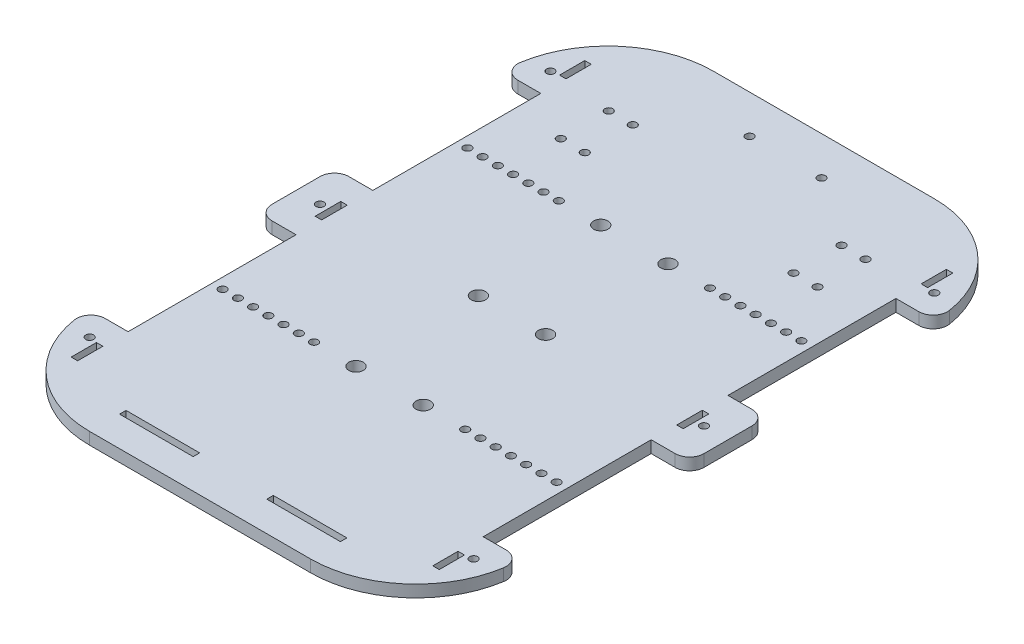
SolidWorks part; units mm, degrees
ref_plane "Ön Düzlem" through (0, 0, 0) normal (0, 0, 1) x (1, 0, 0)
ref_plane "Üst Düzlem" through (0, 0, 0) normal (0, 1, 0) x (1, 0, 0)
ref_plane "Sağ Düzlem" through (0, 0, 0) normal (1, 0, 0) x (0, 0, -1)
sketch "Sketch2" plane through (0, 0, 0) normal (0, 1, 0) x (1, 0, 0)
  line L0 (-74, -86) -> (-74, -51) construction
  line L1 (46, -130) -> (-46, -130)
  line L2 (90, -10) -> (90, 10)
  line L3 (46, 130) -> (-46, 130)
  line L4 (-90, -10) -> (-90, 10)
  line L5 (90, -130) -> (-90, 130) construction
  line L6 (90, 130) -> (-90, -130) construction
  line L7 (-83.5233, 86) -> (-74, 86)
  line L9 (-84, 16) -> (-74, 16)
  line L10 (-74, 86) -> (-74, 16)
  line L11 (-83.5233, -86) -> (-74, -86)
  line L13 (-84, -16) -> (-74, -16)
  line L14 (-74, -86) -> (-74, -16)
  line L15 (83.5233, 86) -> (74, 86)
  line L17 (84, 16) -> (74, 16)
  line L18 (74, 86) -> (74, 16)
  line L19 (83.5233, -86) -> (74, -86)
  line L21 (84, -16) -> (74, -16)
  line L22 (74, -86) -> (74, -16)
  line L23 (-74, 51) -> (74, 51) construction
  line L24 (-74, -51) -> (74, -51) construction
  line L26 (-74, 96.51) -> (-76.7, 96.51)
  line L27 (-76.7, 96.51) -> (-76.7, 107.02)
  line L28 (-74, 107.02) -> (-76.7, 107.02)
  line L29 (-74, 96.51) -> (-74, 107.02)
  line L30 (74, 96.51) -> (74, 107.02)
  line L31 (74, 107.02) -> (76.7, 107.02)
  line L32 (76.7, 96.51) -> (76.7, 107.02)
  line L33 (74, 96.51) -> (76.7, 96.51)
  line L34 (74, -107.02) -> (76.7, -107.02)
  line L35 (76.7, -96.51) -> (76.7, -107.02)
  line L36 (74, -96.51) -> (74, -107.02)
  line L37 (74, -96.51) -> (76.7, -96.51)
  line L38 (-74, -96.51) -> (-74, -107.02)
  line L39 (-74, -107.02) -> (-76.7, -107.02)
  line L40 (-76.7, -96.51) -> (-76.7, -107.02)
  line L41 (-74, -96.51) -> (-76.7, -96.51)
  line L42 (-74, 5.3333) -> (-74, -5.3333)
  line L43 (74, 5.3333) -> (74, -5.3333)
  line L44 (-74, 5.3333) -> (-76.7, 5.3333)
  line L45 (-76.7, 5.3333) -> (-76.7, -5.3333)
  line L46 (-76.7, -5.3333) -> (-74, -5.3333)
  line L47 (74, 5.3333) -> (76.7, 5.3333)
  line L48 (76.7, 5.3333) -> (76.7, -5.3333)
  line L49 (76.7, -5.3333) -> (74, -5.3333)
  line L52 (15.34, -117.53) -> (46.02, -117.53)
  line L54 (-15.34, -117.53) -> (-46.02, -117.53)
  line L56 (46.02, -117.53) -> (46.02, -114.83)
  line L57 (46.02, -114.83) -> (15.34, -114.83)
  line L59 (-15.34, -114.83) -> (-46.02, -114.83)
  line L60 (-46.02, -114.83) -> (-46.02, -117.53)
  line L62 (15.34, -117.53) -> (15.34, -114.83)
  line L63 (-15.34, -117.53) -> (-15.34, -114.83)
  arc A2 (-46, -130) -> (-89.4481, -92.9474) centre (-46, -86) cw
  arc A3 (-89.4481, 92.9474) -> (-46, 130) centre (-46, 86) cw
  arc A4 (89.4481, 92.9474) -> (46, 130) centre (46, 86) ccw
  arc A5 (89.4481, -92.9474) -> (46, -130) centre (46, -86) cw
  arc A6 (-84, 16) -> (-90, 10) centre (-84, 10) ccw
  arc A7 (-84, -16) -> (-90, -10) centre (-84, -10) cw
  arc A8 (90, 10) -> (84, 16) centre (84, 10) ccw
  arc A9 (90, -10) -> (84, -16) centre (84, -10) cw
  arc A10 (-89.4481, -92.9474) -> (-83.5233, -86) centre (-83.5233, -92) cw
  arc A11 (83.5233, -86) -> (89.4481, -92.9474) centre (83.5233, -92) cw
  arc A12 (-89.4481, 92.9474) -> (-83.5233, 86) centre (-83.5233, 92) ccw
  arc A13 (89.4481, 92.9474) -> (83.5233, 86) centre (83.5233, 92) cw
  point P0 (0, 0)
  point P34 (-90, -16)
  point P39 (90, -16)
  point P46 (-90, 86)
  point P49 (90, 86)
  point P72 (0, 0)
  point P75 (0, 0)
  dimension "D3" = 44
  dimension "D4" = 44
  dimension "D5" = 44
  dimension "D6" = 44
  dimension "D15" = 6
  dimension "D16" = 6
  dimension "D17" = 6
  dimension "D18" = 6
  dimension "D19" = 6
  dimension "D20" = 6
  dimension "D21" = 6
  dimension "D22" = 6
  dimension "D1" = 260
  dimension "D2" = 180
  dimension "D7" = 16
  dimension "D8" = 70
  dimension "D9" = 16
  dimension "D10" = 70
  dimension "D11" = 70
  dimension "D12" = 16
  dimension "D13" = 16
  dimension "D14" = 70
extrude "Boss-Extrude4" add sketch "Sketch2" along normal blind 5
sketch "Sketch5" plane through (0, 5, 0) normal (0, 1, 0) x (1, 0, 0)
  line L0 (-53.5, 73.83) -> (-43.5, 73.83) construction
  line L1 (-43.5, 73.83) -> (-43.5, 93.83) construction
  line L2 (-43.5, 93.83) -> (-43.5808, 93.8151) construction
  line L3 (-43.5808, 93.8151) -> (-53.5, 93.83) construction
  line L4 (-74, 86) -> (-74, 16) construction
  line L5 (53.5, 93.83) -> (43.5, 93.83) construction
  line L6 (43.5, 93.83) -> (43.5, 73.83) construction
  line L7 (43.5, 73.83) -> (53.5, 73.83) construction
  line L8 (74, 16) -> (74, 86) construction
  line L9 (46, 130) -> (-46, 130) construction
  circle A0 centre (-69.6, -51) radius 1.65
  circle A1 centre (-63.25, -51) radius 1.65
  circle A2 centre (-56.9, -51) radius 1.65
  circle A3 centre (-50.55, -51) radius 1.65
  circle A4 centre (-44.2, -51) radius 1.65
  circle A5 centre (-37.85, -51) radius 1.65
  circle A6 centre (-31.5, -51) radius 1.65
  circle A7 centre (31.5, -51) radius 1.65
  circle A8 centre (37.85, -51) radius 1.65
  circle A9 centre (44.2, -51) radius 1.65
  circle A10 centre (50.55, -51) radius 1.65
  circle A11 centre (56.9, -51) radius 1.65
  circle A12 centre (63.25, -51) radius 1.65
  circle A13 centre (69.6, -51) radius 1.65
  circle A14 centre (69.6, 51) radius 1.65
  circle A15 centre (63.25, 51) radius 1.65
  circle A16 centre (56.9, 51) radius 1.65
  circle A17 centre (50.55, 51) radius 1.65
  circle A18 centre (44.2, 51) radius 1.65
  circle A19 centre (37.85, 51) radius 1.65
  circle A20 centre (31.5, 51) radius 1.65
  circle A21 centre (-31.5, 51) radius 1.65
  circle A22 centre (-37.85, 51) radius 1.65
  circle A23 centre (-44.2, 51) radius 1.65
  circle A24 centre (-50.55, 51) radius 1.65
  circle A25 centre (-56.9, 51) radius 1.65
  circle A26 centre (-63.25, 51) radius 1.65
  circle A27 centre (-69.6, 51) radius 1.65
  circle A29 centre (-14, -51) radius 3
  circle A30 centre (14, -51) radius 3
  circle A31 centre (14, 51) radius 3
  circle A32 centre (-14, 51) radius 3
  circle A33 centre (-14, 0) radius 3
  circle A34 centre (14, 0) radius 3
  circle A35 centre (-80, 96) radius 1.65
  circle A36 centre (-80, 0) radius 1.65
  circle A37 centre (80, 0) radius 1.65
  circle A38 centre (-80, -96) radius 1.65
  circle A39 centre (80, -96) radius 1.65
  circle A40 centre (80, 96) radius 1.65
  circle A43 centre (15, 114) radius 1.65
  circle A44 centre (-15, 114) radius 1.65
  circle A45 centre (-53.5, 93.83) radius 1.65
  circle A46 centre (-53.5, 73.83) radius 1.65
  circle A47 centre (-43.5, 73.83) radius 1.65
  circle A48 centre (-43.5, 93.83) radius 1.65
  circle A49 centre (43.5, 73.83) radius 1.65
  circle A50 centre (53.5, 73.83) radius 1.65
  circle A51 centre (43.5, 93.83) radius 1.65
  circle A52 centre (53.5, 93.83) radius 1.65
  point P103 (0, 0)
  dimension "D1" = 20.5
  dimension "D2" = 20.5
  dimension "D3" = 36.17
  dimension "D4" = 56.17
  dimension "D5" = 56.17
extrude "Cut-Extrude1" cut sketch "Sketch5" against normal through all
